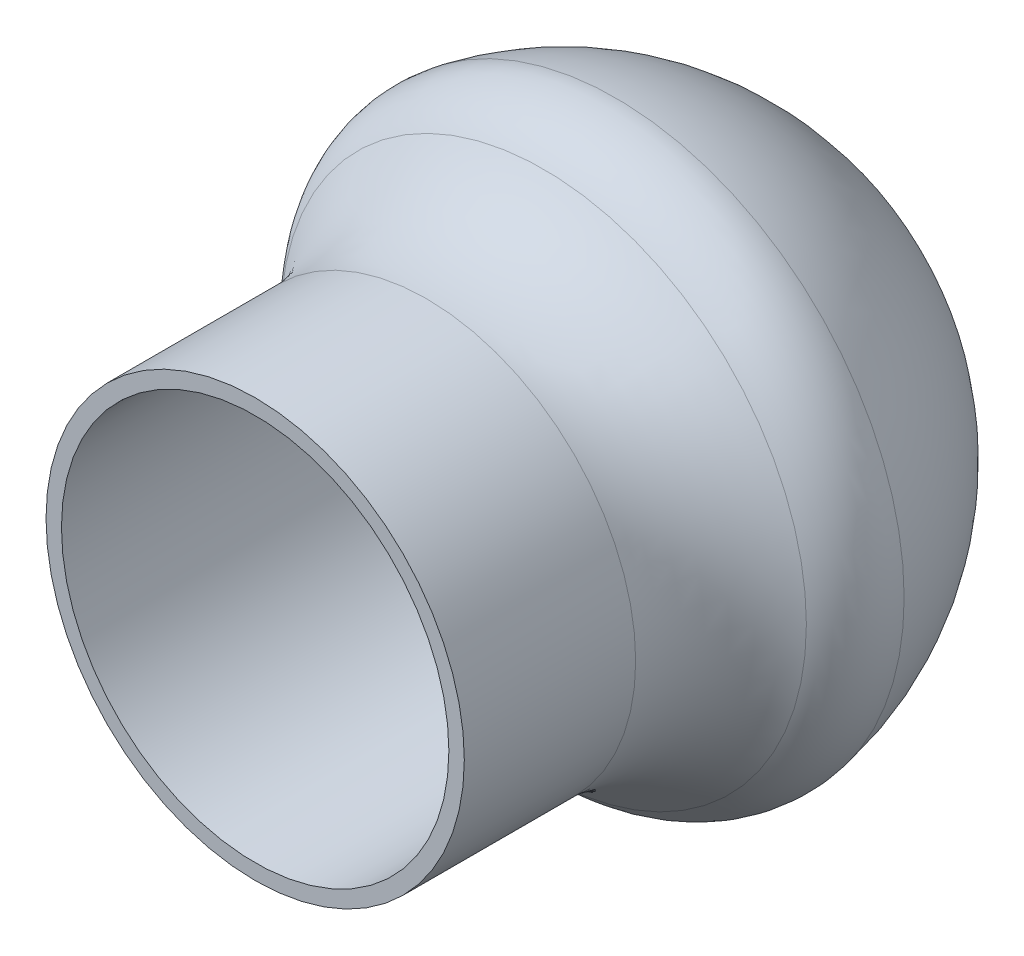
SolidWorks part; units mm, degrees
ref_plane "Plan de face" through (0, 0, 0) normal (0, 0, 1) x (1, 0, 0)
ref_plane "Plan de dessus" through (0, 0, 0) normal (0, 1, 0) x (1, 0, 0)
ref_plane "Plan de droite" through (0, 0, 0) normal (1, 0, 0) x (0, 0, -1)
sketch "Esquisse1" plane through (0, 0, 0) normal (0, 0, 1) x (1, 0, 0)
  circle A0 centre (0, 0) radius 12.55
  circle A1 centre (0, 0) radius 13.55
  dimension "D1" = 25.1
  dimension "D2" = 27.1
extrude "Boss.-Extru.1" add sketch "Esquisse1" along normal blind 20
sketch "Esquisse2" plane through (0, 0, 0) normal (1, 0, 0) x (0, 0, -1)
  line L0 (18.9865, 0) -> (0, 0)
  line L1 (0, 0) -> (0, -18.9865)
  arc A0 (0, -18.9865) -> (18.9865, 0) centre (0, 0) ccw
revolve "Révolution1" add sketch "Esquisse2" angle 360 about L0
fillet "Congé1" radius 10 1 edges at (-13.55, 0, 0)
fillet "Congé2" radius 5 1 edges at (-18.9865, 0, 0)
equation "\"diam_int\" = 25.1"
equation "\"D1@Esquisse1\"=\"diam_int\""
equation "\"diam_ext\"= \"diam_int\" + 2"
equation "\"D2@Esquisse1\"=\"diam_ext\""
